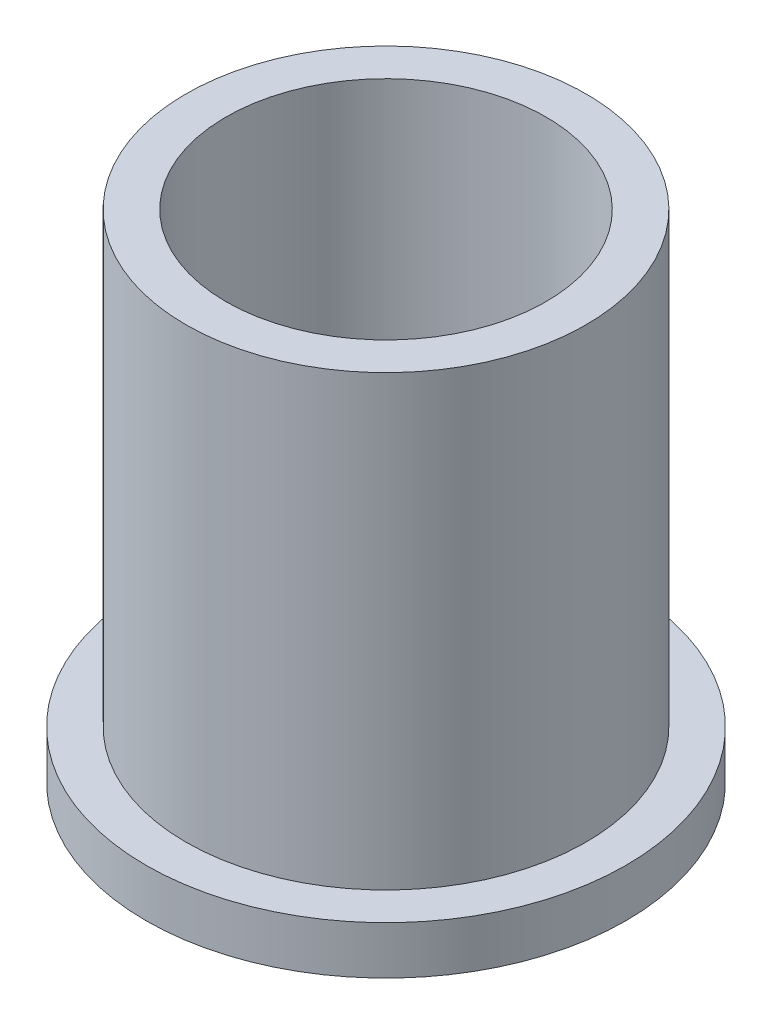
SolidWorks part; units mm, degrees
ref_plane "Plano frontal" through (0, 0, 0) normal (0, 0, 1) x (1, 0, 0)
ref_plane "Plano superior" through (0, 0, 0) normal (0, 1, 0) x (1, 0, 0)
ref_plane "Plano direito" through (0, 0, 0) normal (1, 0, 0) x (0, 0, -1)
sketch "Esboço2" plane through (0, 0, 0) normal (0, 1, 0) x (1, 0, 0)
  circle A0 centre (0, 0) radius 15
  circle A1 centre (0, 0) radius 12.5
  circle A2 centre (0, 0) radius 10
  dimension "D1" = 30
  dimension "D2" = 25
  dimension "D3" = 20
extrude "Ressalto-extrusão1" add sketch "Esboço2" along normal blind 3 contours A0 A1 region at (-14.5757, 0, 0)
extrude "Ressalto-extrusão2" add sketch "Esboço2<3>" along normal blind 31 contours A1 A2 region at (-12.1464, 0, 0)
sketch "Esboço2<3>" plane through (0, 0, 0) normal (0, 1, 0) x (1, 0, 0) same geometry as "Esboço2"
